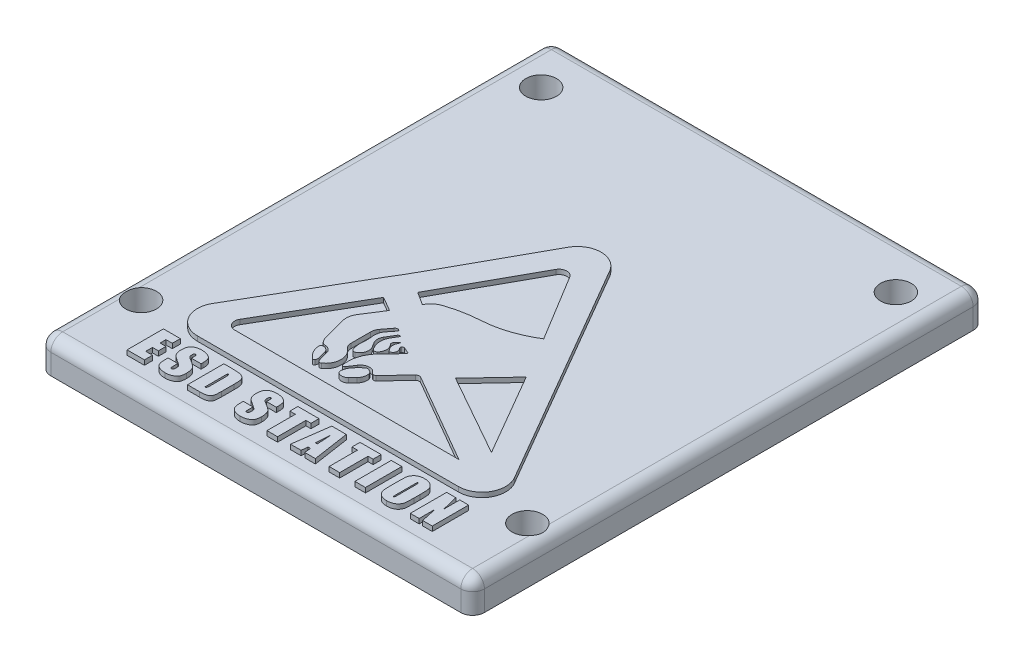
SolidWorks part; units mm, degrees
ref_plane "Front Plane" through (0, 0, 0) normal (0, 0, 1) x (1, 0, 0)
ref_plane "Top Plane" through (0, 0, 0) normal (0, 1, 0) x (1, 0, 0)
ref_plane "Right Plane" through (0, 0, 0) normal (1, 0, 0) x (0, 0, -1)
sketch "Sketch1" plane through (0, 0, 0) normal (0, 1, 0) x (1, 0, 0)
  line L1 (0, 0) -> (139.7, 0)
  line L2 (0, 0) -> (0, 165.1)
  line L3 (0, 165.1) -> (139.7, 165.1)
  line L4 (139.7, 0) -> (139.7, 165.1)
  dimension "D1" = 139.7
  dimension "D2" = 165.1
extrude "Boss-Extrude1" add sketch "Sketch1" along normal blind 9.144
fillet "Fillet1" radius 3.81 4 edges at (139.7, 4.572, -165.1) (139.7, 4.572, 0) (0, 4.572, -165.1) (0, 4.572, 0)
sketch "Sketch2" plane through (0, 9.144, 0) normal (0, 1, 0) x (1, 0, 0)
  line L0 (0, 161.29) -> (0, 3.81) construction
  line L1 (3.81, 0) -> (135.89, 0) construction
  line L2 (69.85, 0) -> (69.85, 165.1) construction
  line L3 (135.89, 165.1) -> (3.81, 165.1) construction
  line L4 (69.85, 82.55) -> (0, 82.55) construction
  circle A0 centre (12.7, 16.002) radius 3.175 construction
  circle A1 centre (127, 16.002) radius 3.175 construction
  circle A2 centre (127, 149.098) radius 3.175
  circle A3 centre (12.7, 149.098) radius 3.175
  dimension "D1" = 12.7
  dimension "D3" = 6.35
  dimension "D2" = 16.002
extrude "Cut-Extrude1" cut sketch "Sketch2" against normal up to surface (9.144 mm away) up to face at (69.85, 0, -82.55)
sketch "Sketch3" plane through (0, 9.144, 0) normal (0, 1, 0) x (1, 0, 0)
  line L0 (70.496, 137.8694) -> (270.496, 137.8694) construction
  line L1 (28.161, 30.48) -> (47.4134, 63.5939)
  line L2 (47.4134, 63.5939) -> (52.0401, 60.904)
  line L3 (52.0401, 60.904) -> (47.9409, 54.4852)
  line L4 (47.4134, 50.3026) -> (49.2236, 43.3018)
  line L5 (53.4968, 39.5889) -> (54.3392, 36.5694)
  line L6 (56.4761, 42.9358) -> (55.7165, 43.6972)
  line L7 (54.9768, 45.464) -> (54.9768, 51.8379)
  line L8 (55.7165, 54.0378) -> (57.7293, 56.6923)
  line L9 (59.2557, 55.9566) -> (57.0374, 53.1942)
  line L10 (59.4465, 47.8878) -> (58.5145, 49.4385)
  line L11 (58.5145, 52.437) -> (60.177, 55.203)
  line L12 (61.3238, 54.8213) -> (60.3568, 53.2123)
  line L13 (60.177, 48.6632) -> (60.5632, 47.8878)
  line L14 (61.3238, 52.9984) -> (62.2674, 53.9845)
  line L15 (64.9229, 53.4025) -> (66.4394, 52.6187)
  line L16 (66.7904, 51.5356) -> (62.2912, 46.8332)
  line L17 (60.5628, 38.0202) -> (62.1412, 40.4606)
  line L18 (65.7939, 41.6234) -> (66.8771, 40.5871)
  line L19 (68.0387, 40.5871) -> (74.234, 47.0623)
  line L20 (75.7475, 47.2487) -> (104.8079, 30.48)
  line L21 (104.8079, 30.48) -> (28.161, 30.48)
  line L22 (50.6207, 39.2402) -> (50.6207, 39.6797) construction
  line L23 (53.0532, 39.2402) -> (53.8778, 36.2848) construction
  line L24 (52.8363, 35.231) -> (52.0463, 36.0717) construction
  line L25 (65.5353, 36.9764) -> (64.1904, 35.5708) construction
  line L26 (51.5296, 70.4908) -> (69.493, 102.9855)
  line L27 (69.493, 102.9855) -> (84.8095, 77.8112)
  line L28 (55.7165, 67.7984) -> (51.5296, 70.4908)
  line L29 (81.5879, 52.6185) -> (92.6396, 64.3418)
  line L30 (92.6396, 64.3418) -> (108.0952, 37.6852)
  line L31 (108.0952, 37.6852) -> (81.5879, 52.6185)
  line L32 (51.1287, 39.264) -> (51.1287, 39.6797)
  line L33 (52.5794, 39.0482) -> (53.3885, 36.1483)
  line L34 (53.2776, 35.5031) -> (52.4165, 36.4195)
  line L35 (65.1682, 37.3276) -> (63.8234, 35.922)
  line L36 (3.81, 0) -> (135.89, 0) construction
  line L37 (139.7, 3.81) -> (139.7, 161.29) construction
  arc A0 (47.9409, 54.4852) -> (47.4134, 50.3026) centre (52.0861, 51.8379) ccw
  arc A1 (49.2236, 43.3018) -> (49.9905, 41.6232) centre (54.3392, 44.6245) ccw
  arc A2 (49.9905, 41.6232) -> (51.4393, 40.8175) centre (51.5296, 42.6854) ccw
  arc A3 (51.4393, 40.8175) -> (53.4968, 39.5889) centre (51.3162, 38.2743) cw
  arc A4 (54.3392, 36.5694) -> (54.7579, 35.4842) centre (60.1769, 38.1982) ccw
  arc A5 (54.7579, 35.4842) -> (55.7165, 35.231) centre (55.3488, 35.7802) ccw
  arc A6 (55.7165, 35.231) -> (56.4761, 42.9358) centre (52.928, 39.3958) ccw
  arc A7 (55.7165, 43.6972) -> (54.9768, 45.464) centre (57.5095, 45.4861) cw
  arc A8 (54.9768, 51.8379) -> (55.7165, 54.0378) centre (58.6177, 51.8379) cw
  arc A9 (57.7293, 56.6923) -> (58.6177, 57.0798) centre (58.5193, 56.0933) cw
  arc A10 (58.6177, 57.0798) -> (59.2557, 55.9566) centre (58.5392, 56.2924) cw
  arc A11 (57.0374, 53.1942) -> (56.4761, 51.1928) centre (59.1031, 51.5354) ccw
  arc A12 (56.4761, 51.1928) -> (56.5523, 47.5601) centre (39.8723, 49.0275) cw
  arc A13 (56.5523, 47.5601) -> (57.0374, 44.1483) centre (64.1142, 46.8949) ccw
  arc A14 (57.0374, 44.1483) -> (58.1466, 43.6972) centre (57.8049, 44.4461) ccw
  arc A15 (58.1466, 43.6972) -> (59.4465, 47.8878) centre (56.9259, 46.3728) ccw
  arc A16 (58.5145, 49.4385) -> (58.5145, 52.437) centre (61.0089, 50.9378) cw
  arc A17 (60.177, 55.203) -> (61.3238, 54.8213) centre (60.7077, 54.8839) cw
  arc A18 (60.3568, 53.2123) -> (60.177, 48.6632) centre (64.4138, 50.7739) ccw
  arc A19 (60.5632, 47.8878) -> (61.3238, 47.7724) centre (60.9841, 48.0975) ccw
  arc A20 (61.3238, 47.7724) -> (61.3238, 51.1928) centre (59.5364, 49.4826) ccw
  arc A21 (61.3238, 51.1928) -> (61.3238, 52.9984) centre (62.2674, 52.0956) cw
  arc A22 (62.2674, 53.9845) -> (62.8438, 53.6001) centre (62.5216, 53.7414) cw
  arc A23 (62.8438, 53.6001) -> (62.4203, 52.5384) centre (78.3715, 46.7913) ccw
  arc A24 (62.4203, 52.5384) -> (62.719, 50.2428) centre (64.8004, 51.6809) ccw
  arc A25 (62.719, 50.2428) -> (64.1904, 50.6654) centre (63.3835, 50.702) ccw
  arc A26 (64.1904, 50.6654) -> (63.828, 51.6803) centre (62.7686, 50.7298) ccw
  arc A27 (63.828, 51.6803) -> (63.828, 53.0022) centre (64.5648, 52.3412) cw
  arc A28 (63.828, 53.0022) -> (64.9229, 53.4025) centre (64.7516, 52.1737) cw
  arc A29 (66.4394, 52.6187) -> (66.7904, 51.5356) centre (66.068, 51.8999) cw
  arc A30 (62.2912, 46.8332) -> (59.6799, 38.1984) centre (69.4926, 39.9431) ccw
  arc A31 (59.6799, 38.1984) -> (60.5628, 38.0202) centre (60.1564, 38.2831) ccw
  arc A32 (62.1412, 40.4606) -> (65.7939, 41.6234) centre (64.6742, 38.8223) cw
  arc A33 (66.8771, 40.5871) -> (68.0387, 40.5871) centre (67.4579, 41.1941) ccw
  arc A34 (74.234, 47.0623) -> (75.7475, 47.2487) centre (75.1048, 46.2291) cw
  arc A35 (50.6207, 39.6797) -> (51.1953, 40.2899) centre (51.2321, 39.6797) cw construction
  arc A36 (51.1953, 40.2899) -> (53.0532, 39.2402) centre (51.3133, 38.3297) cw construction
  arc A37 (53.8778, 36.2848) -> (53.7449, 35.231) centre (52.5567, 35.9162) cw construction
  arc A38 (53.7449, 35.231) -> (52.8363, 35.231) centre (53.2906, 35.493) cw construction
  arc A39 (52.0463, 36.0717) -> (50.6207, 39.2402) centre (55.9362, 39.7268) cw construction
  arc A40 (64.1904, 35.5708) -> (61.5034, 35.231) centre (62.6376, 37.0566) cw construction
  arc A41 (61.5034, 35.231) -> (60.9841, 36.2736) centre (62.0888, 36.1732) cw construction
  arc A42 (60.9841, 36.2736) -> (62.0888, 38.9278) centre (65.7697, 35.8388) cw construction
  arc A43 (62.0888, 38.9278) -> (64.1142, 40.9166) centre (73.3944, 29.4401) cw construction
  arc A44 (64.1142, 40.9166) -> (65.4437, 40.9166) centre (64.7789, 40.0946) cw construction
  arc A45 (65.5353, 36.9764) -> (66.4399, 39.7268) centre (63.1082, 39.2986) ccw construction
  arc A46 (66.4399, 39.7268) -> (65.4437, 40.9166) centre (65.012, 39.5433) ccw construction
  arc A47 (84.8095, 77.8112) -> (80.0875, 75.3624) centre (64.5176, 111.1633) cw
  arc A48 (80.0875, 75.3624) -> (69.493, 72.8238) centre (67.6134, 104.0449) cw
  arc A49 (69.493, 72.8238) -> (59.2557, 70.8551) centre (71.9121, 32.6431) ccw
  arc A50 (59.2557, 70.8551) -> (55.7165, 67.7984) centre (61.1776, 65.0525) ccw
  arc A51 (52.4165, 36.4195) -> (51.1287, 39.264) centre (55.9362, 39.7268) cw
  arc A52 (51.1287, 39.6797) -> (51.2259, 39.7828) centre (51.2321, 39.6797) cw
  arc A53 (51.2259, 39.7828) -> (52.5794, 39.0482) centre (51.3133, 38.3297) cw
  arc A54 (53.3885, 36.1483) -> (53.3048, 35.4848) centre (52.5567, 35.9162) cw
  arc A55 (53.3048, 35.4848) -> (53.2776, 35.5031) centre (53.2906, 35.493) cw
  arc A56 (61.7715, 35.6625) -> (61.49, 36.2276) centre (62.0888, 36.1732) cw
  arc A57 (61.49, 36.2276) -> (62.4779, 38.6012) centre (65.7697, 35.8388) cw
  arc A58 (62.4779, 38.6012) -> (64.4336, 40.5216) centre (73.3944, 29.4401) cw
  arc A59 (64.4336, 40.5216) -> (65.1911, 40.4575) centre (64.7789, 40.0946) cw
  arc A60 (65.936, 39.6621) -> (65.1911, 40.4575) centre (65.012, 39.5433) ccw
  arc A61 (65.1682, 37.3276) -> (65.936, 39.6621) centre (63.1082, 39.2986) ccw
  arc A62 (63.8234, 35.922) -> (61.7715, 35.6625) centre (62.6376, 37.0566) cw
  point P134 (50.787, 40.0988)
  point P136 (53.2906, 34.9686)
  dimension "D17" = 4.9184
  dimension "D18" = 5.2839
  dimension "D19" = 1.8701
  dimension "D20" = 2.5462
  dimension "D21" = 6.0606
  dimension "D22" = 0.6609
  dimension "D23" = 2.5329
  dimension "D24" = 3.6409
  dimension "D25" = 0.9915
  dimension "D26" = 0.7913
  dimension "D27" = 2.6492
  dimension "D28" = 16.7444
  dimension "D29" = 7.5911
  dimension "D30" = 0.8232
  dimension "D31" = 2.9409
  dimension "D32" = 2.9103
  dimension "D33" = 0.6193
  dimension "D34" = 4.7335
  dimension "D35" = 0.4702
  dimension "D36" = 2.4738
  dimension "D37" = 1.3059
  dimension "D38" = 0.3518
  dimension "D39" = 16.955
  dimension "D40" = 2.5299
  dimension "D41" = 0.8078
  dimension "D42" = 1.4233
  dimension "D43" = 0.9898
  dimension "D44" = 1.2407
  dimension "D45" = 0.8091
  dimension "D46" = 9.9666
  dimension "D47" = 0.484
  dimension "D48" = 3.0166
  dimension "D49" = 0.8402
  dimension "D50" = 1.2052
  dimension "D51" = 0.6114
  dimension "D52" = 1.9637
  dimension "D53" = 1.3716
  dimension "D54" = 0.5244
  dimension "D55" = 5.3377
  dimension "D56" = 2.1492
  dimension "D57" = 1.1092
  dimension "D58" = 4.8053
  dimension "D59" = 14.7592
  dimension "D60" = 1.0572
  dimension "D61" = 3.3591
  dimension "D62" = 1.4396
  dimension "D63" = 39.04
  dimension "D64" = 31.2776
  dimension "D65" = 40.2535
  dimension "D66" = 6.1126
  dimension "D67" = 31.6048
  dimension "D68" = 34.8921
  dimension "D69" = 47.0604
  dimension "D70" = 54.8905
  dimension "D71" = 58.1121
  dimension "D72" = 59.6125
  dimension "D73" = 61.3285
  dimension "D74" = 64.5952
  dimension "D75" = 65.466
  dimension "D76" = 66.3056
  dimension "D77" = 67.7879
  dimension "D78" = 70.2074
  dimension "D3" = 4.9778
  dimension "D4" = 37.1294
  dimension "D5" = 29.4677
  dimension "D6" = 8.0318
  dimension "D7" = 7.8134
  dimension "D8" = 15.5799
  dimension "D9" = 30.8131
  dimension "D10" = 30.4243
  dimension "D11" = 7.9197
  dimension "D12" = 7.57
  dimension "D13" = 30.48
  dimension "D14" = 33.5513
  dimension "D15" = 76.6469
  dimension "D16" = 38.3039
  dimension "D79" = 71.6613
  dimension "D80" = 72.9096
  dimension "D81" = 73.2606
  dimension "D82" = 73.632
  dimension "D83" = 73.764
  dimension "D84" = 73.9061
  dimension "D85" = 73.9303
  dimension "D86" = 74.5089
  dimension "D87" = 74.5318
  dimension "D88" = 74.7771
  dimension "D89" = 74.8996
  dimension "D90" = 74.9484
  dimension "D91" = 75.0258
  dimension "D92" = 75.1352
  dimension "D93" = 75.2862
  dimension "D94" = 77.5588
  dimension "D95" = 78.5224
  dimension "D96" = 78.6911
  dimension "D97" = 78.9923
  dimension "D98" = 79.5231
  dimension "D99" = 80.5969
  dimension "D100" = 81.0823
  dimension "D101" = 81.1608
  dimension "D102" = 81.5534
  dimension "D103" = 81.9707
  dimension "D104" = 82.1905
  dimension "D105" = 83.2239
  dimension "D106" = 83.7638
  dimension "D107" = 85.3608
  dimension "D108" = 85.3608
  dimension "D109" = 86.2032
  dimension "D110" = 86.3115
  dimension "D111" = 86.772
  dimension "D112" = 87.1206
  dimension "D113" = 87.6139
  dimension "D114" = 88.2607
  dimension "D115" = 88.3867
  dimension "D1" = 0.508
  dimension "D2" = 0.508
extrude "Boss-Extrude3" add sketch "Sketch3" along normal blind 1.27
sketch "Sketch4" plane through (0, 9.144, 0) normal (0, 1, 0) x (1, 0, 0)
  line L28 (114.6873, 41.5074) -> (99.2316, 68.1639)
  line L29 (114.6873, 41.5074) -> (99.2316, 68.1639)
  line L38 (40.8259, 67.4239) -> (44.8608, 74.1774)
  line L39 (40.8259, 67.4239) -> (14.9165, 22.86)
  line L40 (14.9165, 22.86) -> (104.8079, 22.86)
  line L41 (40.8259, 67.4239) -> (21.5735, 34.31)
  line L42 (28.161, 22.86) -> (104.8079, 22.86)
  line L45 (99.2316, 68.1639) -> (76.4466, 107.4616)
  line L47 (114.6873, 41.5074) -> (118.8649, 34.3021)
  line L48 (112.2729, 22.86) -> (104.8079, 22.86)
  line L49 (44.8608, 74.1774) -> (63.1857, 107.326)
  line L50 (69.493, 102.9855) -> (51.5296, 70.4908) construction
  line L52 (139.7, 3.81) -> (139.7, 161.29) construction
  line L55 (3.81, 0) -> (135.89, 0) construction
  line L56 (135.89, 165.1) -> (3.81, 165.1) construction
  line L57 (0, 161.29) -> (0, 3.81) construction
  line L58 (139.7, 3.81) -> (139.7, 161.29)
  line L59 (3.81, 0) -> (135.89, 0)
  line L60 (135.89, 165.1) -> (3.81, 165.1)
  line L61 (0, 161.29) -> (0, 3.81)
  arc A0 (28.161, 22.86) -> (21.5735, 34.31) centre (28.161, 30.48) cw
  arc A1 (118.8649, 34.3021) -> (112.2729, 22.86) centre (112.2729, 30.48) cw
  arc A2 (76.4466, 107.4616) -> (63.1857, 107.326) centre (69.8545, 103.6394) ccw
  arc A5 (139.7, 161.29) -> (135.89, 165.1) centre (135.89, 161.29) ccw construction
  arc A6 (135.89, 0) -> (139.7, 3.81) centre (135.89, 3.81) ccw construction
  arc A7 (0, 3.81) -> (3.81, 0) centre (3.81, 3.81) ccw construction
  arc A8 (3.81, 165.1) -> (0, 161.29) centre (3.81, 161.29) ccw construction
  arc A11 (139.7, 161.29) -> (135.89, 165.1) centre (135.89, 161.29) ccw
  arc A12 (135.89, 0) -> (139.7, 3.81) centre (135.89, 3.81) ccw
  arc A13 (0, 3.81) -> (3.81, 0) centre (3.81, 3.81) ccw
  arc A14 (3.81, 165.1) -> (0, 161.29) centre (3.81, 161.29) ccw
  circle A15 centre (127, 149.098) radius 3.175 construction
  circle A16 centre (12.7, 149.098) radius 3.175 construction
  circle A17 centre (127, 149.098) radius 3.175
  circle A18 centre (12.7, 149.098) radius 3.175
  dimension "D5" = 7.62
  dimension "D3" = 7.62
  dimension "D4" = 7.867
  dimension "D1" = 7.62
  dimension "D2" = 7.62
extrude "Boss-Extrude5" add sketch "Sketch4" along normal up to surface (1.27 mm away) up to face at (59.5349, 10.414, -47.7884)
fillet "Fillet2" radius 2.54 2 edges at (69.493, 9.779, -102.9855) (28.161, 9.779, -30.48)
sketch "Sketch5" plane through (0, 10.414, 0) normal (0, 1, 0) x (1, 0, 0)
  line L2 (3.81, 7.62) -> (135.89, 7.62)
  line L3 (3.81, 7.62) -> (135.89, 7.62) construction
  text T0 "E S D  S T A T I O N" font "Impact" height in points 42
  dimension "D1" = 7.62
extrude "Boss-Extrude6" add sketch "Sketch5" along normal blind 1.524
sketch "Sketch6" plane through (0, 10.414, 0) normal (0, 1, 0) x (1, 0, 0)
  circle A0 centre (7.62, 25.273) radius 3.81 construction
  circle A1 centre (132.08, 25.273) radius 3.81 construction
  circle A2 centre (7.62, 25.273) radius 3.81 construction
  circle A3 centre (132.08, 25.273) radius 3.81 construction
  circle A4 centre (132.08, 25.273) radius 3.175
  circle A5 centre (7.62, 25.273) radius 3.175
  dimension "D1" = 6.35
  dimension "D2" = 6.35
extrude "Cut-Extrude2" cut sketch "Sketch6" against normal up to surface (10.414 mm away) up to face at (127, 0, -152.273)
sketch "Sketch7" plane through (0, 10.414, 0) normal (0, 1, 0) x (1, 0, 0)
  circle A0 centre (127, 149.098) radius 4.953
  circle A1 centre (132.08, 25.273) radius 4.953
  circle A2 centre (7.62, 25.273) radius 4.953
  circle A3 centre (12.7, 149.098) radius 4.953
  dimension "D1" = 9.906
  dimension "D2" = 9.906
  dimension "D3" = 9.906
  dimension "D4" = 9.906
extrude "Cut-Extrude3" cut sketch "Sketch7" against normal blind 6.985
fillet "Fillet3" radius 3.81 8 edges at (1.1159, 10.414, -163.9841) (69.85, 10.414, -165.1) (138.5841, 10.414, -163.9841) (139.7, 10.414, -82.55) (138.5841, 10.414, -1.1159) (69.85, 10.414, 0) (1.1159, 10.414, -1.1159) (0, 10.414, -82.55)
sketch "Sketch10" plane through (0, 9.144, 0) normal (0, 1, 0) x (1, 0, 0)
  line L0 (63.8234, 35.922) -> (65.1682, 37.3276) construction
  line L1 (51.1287, 39.6797) -> (51.1287, 39.264) construction
  line L2 (52.4165, 36.4195) -> (53.2776, 35.5031) construction
  line L3 (53.3885, 36.1483) -> (52.5794, 39.0482) construction
  line L4 (44.8608, 74.1774) -> (40.8259, 67.4239) construction
  line L5 (40.8259, 67.4239) -> (21.5735, 34.31) construction
  line L6 (28.161, 22.86) -> (112.2729, 22.86) construction
  line L7 (118.8649, 34.3021) -> (76.4466, 107.4616) construction
  line L8 (63.1857, 107.326) -> (44.8608, 74.1774) construction
  line L9 (63.8234, 35.922) -> (65.1682, 37.3276)
  line L10 (51.1287, 39.6797) -> (51.1287, 39.264)
  line L11 (52.4165, 36.4195) -> (53.2776, 35.5031)
  line L12 (53.3885, 36.1483) -> (52.5794, 39.0482)
  line L13 (44.8608, 74.1774) -> (40.8259, 67.4239)
  line L14 (40.8259, 67.4239) -> (21.5735, 34.31)
  line L15 (28.161, 22.86) -> (112.2729, 22.86)
  line L16 (118.8649, 34.3021) -> (76.4466, 107.4616)
  line L17 (63.1857, 107.326) -> (44.8608, 74.1774)
  line L18 (81.5879, 52.6185) -> (108.0952, 37.6852) construction
  line L19 (108.0952, 37.6852) -> (92.6396, 64.3418) construction
  line L20 (92.6396, 64.3418) -> (81.5879, 52.6185) construction
  line L21 (84.8095, 77.8112) -> (71.7682, 99.2461) construction
  line L22 (67.3753, 99.1547) -> (51.5296, 70.4908) construction
  line L23 (51.5296, 70.4908) -> (55.7165, 67.7984) construction
  line L24 (47.4134, 63.5939) -> (30.38, 34.2967) construction
  line L25 (32.5759, 30.48) -> (104.8079, 30.48) construction
  line L26 (104.8079, 30.48) -> (75.7475, 47.2487) construction
  line L27 (74.234, 47.0623) -> (68.0387, 40.5871) construction
  line L28 (66.8771, 40.5871) -> (65.7939, 41.6234) construction
  line L29 (62.1412, 40.4606) -> (60.5628, 38.0202) construction
  line L30 (62.2912, 46.8332) -> (66.7904, 51.5356) construction
  line L31 (66.4394, 52.6187) -> (64.9229, 53.4025) construction
  line L32 (62.2674, 53.9845) -> (61.3238, 52.9984) construction
  line L33 (60.5632, 47.8878) -> (60.177, 48.6632) construction
  line L34 (60.3568, 53.2123) -> (61.3238, 54.8213) construction
  line L35 (60.177, 55.203) -> (58.5145, 52.437) construction
  line L36 (58.5145, 49.4385) -> (59.4465, 47.8878) construction
  line L37 (57.0374, 53.1942) -> (59.2557, 55.9566) construction
  line L38 (57.7293, 56.6923) -> (55.7165, 54.0378) construction
  line L39 (54.9768, 51.8379) -> (54.9768, 45.464) construction
  line L40 (55.7165, 43.6972) -> (56.4761, 42.9358) construction
  line L41 (54.3392, 36.5694) -> (53.4968, 39.5889) construction
  line L42 (49.2236, 43.3018) -> (47.4134, 50.3026) construction
  line L43 (47.9409, 54.4852) -> (52.0401, 60.904) construction
  line L44 (52.0401, 60.904) -> (47.4134, 63.5939) construction
  line L45 (81.5879, 52.6185) -> (108.0952, 37.6852)
  line L46 (108.0952, 37.6852) -> (92.6396, 64.3418)
  line L47 (92.6396, 64.3418) -> (81.5879, 52.6185)
  line L48 (84.8095, 77.8112) -> (71.7682, 99.2461)
  line L49 (67.3753, 99.1547) -> (51.5296, 70.4908)
  line L50 (51.5296, 70.4908) -> (55.7165, 67.7984)
  line L51 (47.4134, 63.5939) -> (30.38, 34.2967)
  line L52 (32.5759, 30.48) -> (104.8079, 30.48)
  line L53 (104.8079, 30.48) -> (75.7475, 47.2487)
  line L54 (74.234, 47.0623) -> (68.0387, 40.5871)
  line L55 (66.8771, 40.5871) -> (65.7939, 41.6234)
  line L56 (62.1412, 40.4606) -> (60.5628, 38.0202)
  line L57 (62.2912, 46.8332) -> (66.7904, 51.5356)
  line L58 (66.4394, 52.6187) -> (64.9229, 53.4025)
  line L59 (62.2674, 53.9845) -> (61.3238, 52.9984)
  line L60 (60.5632, 47.8878) -> (60.177, 48.6632)
  line L61 (60.3568, 53.2123) -> (61.3238, 54.8213)
  line L62 (60.177, 55.203) -> (58.5145, 52.437)
  line L63 (58.5145, 49.4385) -> (59.4465, 47.8878)
  line L64 (57.0374, 53.1942) -> (59.2557, 55.9566)
  line L65 (57.7293, 56.6923) -> (55.7165, 54.0378)
  line L66 (54.9768, 51.8379) -> (54.9768, 45.464)
  line L67 (55.7165, 43.6972) -> (56.4761, 42.9358)
  line L68 (54.3392, 36.5694) -> (53.4968, 39.5889)
  line L69 (49.2236, 43.3018) -> (47.4134, 50.3026)
  line L70 (47.9409, 54.4852) -> (52.0401, 60.904)
  line L71 (52.0401, 60.904) -> (47.4134, 63.5939)
  arc A0 (61.49, 36.2276) -> (61.7715, 35.6625) centre (62.0888, 36.1732) ccw construction
  arc A1 (61.7715, 35.6625) -> (63.8234, 35.922) centre (62.6376, 37.0566) ccw construction
  arc A2 (65.1682, 37.3276) -> (65.936, 39.6621) centre (63.1082, 39.2986) ccw construction
  arc A3 (65.936, 39.6621) -> (65.1911, 40.4575) centre (65.012, 39.5433) ccw construction
  arc A4 (65.1911, 40.4575) -> (64.4336, 40.5216) centre (64.7789, 40.0946) ccw construction
  arc A5 (64.4336, 40.5216) -> (62.4779, 38.6012) centre (73.3944, 29.4401) ccw construction
  arc A6 (62.4779, 38.6012) -> (61.49, 36.2276) centre (65.7697, 35.8388) ccw construction
  arc A7 (51.1287, 39.264) -> (52.4165, 36.4195) centre (55.9362, 39.7268) ccw construction
  arc A8 (53.2776, 35.5031) -> (53.3048, 35.4848) centre (53.2906, 35.493) ccw construction
  arc A9 (53.3048, 35.4848) -> (53.3885, 36.1483) centre (52.5567, 35.9162) ccw construction
  arc A10 (52.5794, 39.0482) -> (51.2259, 39.7828) centre (51.3133, 38.3297) ccw construction
  arc A11 (51.2259, 39.7828) -> (51.1287, 39.6797) centre (51.2321, 39.6797) ccw construction
  arc A12 (21.5735, 34.31) -> (28.161, 22.86) centre (28.161, 30.48) ccw construction
  arc A13 (112.2729, 22.86) -> (118.8649, 34.3021) centre (112.2729, 30.48) ccw construction
  arc A14 (76.4466, 107.4616) -> (63.1857, 107.326) centre (69.8545, 103.6394) ccw construction
  arc A15 (61.49, 36.2276) -> (61.7715, 35.6625) centre (62.0888, 36.1732) ccw
  arc A16 (61.7715, 35.6625) -> (63.8234, 35.922) centre (62.6376, 37.0566) ccw
  arc A17 (65.1682, 37.3276) -> (65.936, 39.6621) centre (63.1082, 39.2986) ccw
  arc A18 (65.936, 39.6621) -> (65.1911, 40.4575) centre (65.012, 39.5433) ccw
  arc A19 (65.1911, 40.4575) -> (64.4336, 40.5216) centre (64.7789, 40.0946) ccw
  arc A20 (64.4336, 40.5216) -> (62.4779, 38.6012) centre (73.3944, 29.4401) ccw
  arc A21 (62.4779, 38.6012) -> (61.49, 36.2276) centre (65.7697, 35.8388) ccw
  arc A22 (51.1287, 39.264) -> (52.4165, 36.4195) centre (55.9362, 39.7268) ccw
  arc A23 (53.2776, 35.5031) -> (53.3048, 35.4848) centre (53.2906, 35.493) ccw
  arc A24 (53.3048, 35.4848) -> (53.3885, 36.1483) centre (52.5567, 35.9162) ccw
  arc A25 (52.5794, 39.0482) -> (51.2259, 39.7828) centre (51.3133, 38.3297) ccw
  arc A26 (51.2259, 39.7828) -> (51.1287, 39.6797) centre (51.2321, 39.6797) ccw
  arc A27 (21.5735, 34.31) -> (28.161, 22.86) centre (28.161, 30.48) ccw
  arc A28 (112.2729, 22.86) -> (118.8649, 34.3021) centre (112.2729, 30.48) ccw
  arc A29 (76.4466, 107.4616) -> (63.1857, 107.326) centre (69.8545, 103.6394) ccw
  arc A30 (71.7682, 99.2461) -> (67.3753, 99.1547) centre (69.5983, 97.9258) ccw construction
  arc A31 (59.2557, 70.8551) -> (55.7165, 67.7984) centre (61.1776, 65.0525) ccw construction
  arc A32 (69.493, 72.8238) -> (59.2557, 70.8551) centre (71.9121, 32.6431) ccw construction
  arc A33 (69.493, 72.8238) -> (80.0875, 75.3624) centre (67.6134, 104.0449) ccw construction
  arc A34 (80.0875, 75.3624) -> (84.8095, 77.8112) centre (64.5176, 111.1633) ccw construction
  arc A35 (30.38, 34.2967) -> (32.5759, 30.48) centre (32.5759, 33.02) ccw construction
  arc A36 (75.7475, 47.2487) -> (74.234, 47.0623) centre (75.1048, 46.2291) ccw construction
  arc A37 (66.8771, 40.5871) -> (68.0387, 40.5871) centre (67.4579, 41.1941) ccw construction
  arc A38 (65.7939, 41.6234) -> (62.1412, 40.4606) centre (64.6742, 38.8223) ccw construction
  arc A39 (59.6799, 38.1984) -> (60.5628, 38.0202) centre (60.1564, 38.2831) ccw construction
  arc A40 (62.2912, 46.8332) -> (59.6799, 38.1984) centre (69.4926, 39.9431) ccw construction
  arc A41 (66.7904, 51.5356) -> (66.4394, 52.6187) centre (66.068, 51.8999) ccw construction
  arc A42 (64.9229, 53.4025) -> (63.828, 53.0022) centre (64.7516, 52.1737) ccw construction
  arc A43 (63.828, 53.0022) -> (63.828, 51.6803) centre (64.5648, 52.3412) ccw construction
  arc A44 (64.1904, 50.6654) -> (63.828, 51.6803) centre (62.7686, 50.7298) ccw construction
  arc A45 (62.719, 50.2428) -> (64.1904, 50.6654) centre (63.3835, 50.702) ccw construction
  arc A46 (62.4203, 52.5384) -> (62.719, 50.2428) centre (64.8004, 51.6809) ccw construction
  arc A47 (62.8438, 53.6001) -> (62.4203, 52.5384) centre (78.3715, 46.7913) ccw construction
  arc A48 (62.8438, 53.6001) -> (62.2674, 53.9845) centre (62.5216, 53.7414) ccw construction
  arc A49 (61.3238, 52.9984) -> (61.3238, 51.1928) centre (62.2674, 52.0956) ccw construction
  arc A50 (61.3238, 47.7724) -> (61.3238, 51.1928) centre (59.5364, 49.4826) ccw construction
  arc A51 (60.5632, 47.8878) -> (61.3238, 47.7724) centre (60.9841, 48.0975) ccw construction
  arc A52 (60.3568, 53.2123) -> (60.177, 48.6632) centre (64.4138, 50.7739) ccw construction
  arc A53 (61.3238, 54.8213) -> (60.177, 55.203) centre (60.7077, 54.8839) ccw construction
  arc A54 (58.5145, 52.437) -> (58.5145, 49.4385) centre (61.0089, 50.9378) ccw construction
  arc A55 (58.1466, 43.6972) -> (59.4465, 47.8878) centre (56.9259, 46.3728) ccw construction
  arc A56 (57.0374, 44.1483) -> (58.1466, 43.6972) centre (57.8049, 44.4461) ccw construction
  arc A57 (56.5523, 47.5601) -> (57.0374, 44.1483) centre (64.1142, 46.8949) ccw construction
  arc A58 (56.5523, 47.5601) -> (56.4761, 51.1928) centre (39.8723, 49.0275) ccw construction
  arc A59 (57.0374, 53.1942) -> (56.4761, 51.1928) centre (59.1031, 51.5354) ccw construction
  arc A60 (59.2557, 55.9566) -> (58.6177, 57.0798) centre (58.5392, 56.2924) ccw construction
  arc A61 (58.6177, 57.0798) -> (57.7293, 56.6923) centre (58.5193, 56.0933) ccw construction
  arc A62 (55.7165, 54.0378) -> (54.9768, 51.8379) centre (58.6177, 51.8379) ccw construction
  arc A63 (54.9768, 45.464) -> (55.7165, 43.6972) centre (57.5095, 45.4861) ccw construction
  arc A64 (55.7165, 35.231) -> (56.4761, 42.9358) centre (52.928, 39.3958) ccw construction
  arc A65 (54.7579, 35.4842) -> (55.7165, 35.231) centre (55.3488, 35.7802) ccw construction
  arc A66 (54.3392, 36.5694) -> (54.7579, 35.4842) centre (60.1769, 38.1982) ccw construction
  arc A67 (53.4968, 39.5889) -> (51.4393, 40.8175) centre (51.3162, 38.2743) ccw construction
  arc A68 (49.9905, 41.6232) -> (51.4393, 40.8175) centre (51.5296, 42.6854) ccw construction
  arc A69 (49.2236, 43.3018) -> (49.9905, 41.6232) centre (54.3392, 44.6245) ccw construction
  arc A70 (47.9409, 54.4852) -> (47.4134, 50.3026) centre (52.0861, 51.8379) ccw construction
  arc A71 (71.7682, 99.2461) -> (67.3753, 99.1547) centre (69.5983, 97.9258) ccw
  arc A72 (59.2557, 70.8551) -> (55.7165, 67.7984) centre (61.1776, 65.0525) ccw
  arc A73 (69.493, 72.8238) -> (59.2557, 70.8551) centre (71.9121, 32.6431) ccw
  arc A74 (69.493, 72.8238) -> (80.0875, 75.3624) centre (67.6134, 104.0449) ccw
  arc A75 (80.0875, 75.3624) -> (84.8095, 77.8112) centre (64.5176, 111.1633) ccw
  arc A76 (30.38, 34.2967) -> (32.5759, 30.48) centre (32.5759, 33.02) ccw
  arc A77 (75.7475, 47.2487) -> (74.234, 47.0623) centre (75.1048, 46.2291) ccw
  arc A78 (66.8771, 40.5871) -> (68.0387, 40.5871) centre (67.4579, 41.1941) ccw
  arc A79 (65.7939, 41.6234) -> (62.1412, 40.4606) centre (64.6742, 38.8223) ccw
  arc A80 (59.6799, 38.1984) -> (60.5628, 38.0202) centre (60.1564, 38.2831) ccw
  arc A81 (62.2912, 46.8332) -> (59.6799, 38.1984) centre (69.4926, 39.9431) ccw
  arc A82 (66.7904, 51.5356) -> (66.4394, 52.6187) centre (66.068, 51.8999) ccw
  arc A83 (64.9229, 53.4025) -> (63.828, 53.0022) centre (64.7516, 52.1737) ccw
  arc A84 (63.828, 53.0022) -> (63.828, 51.6803) centre (64.5648, 52.3412) ccw
  arc A85 (64.1904, 50.6654) -> (63.828, 51.6803) centre (62.7686, 50.7298) ccw
  arc A86 (62.719, 50.2428) -> (64.1904, 50.6654) centre (63.3835, 50.702) ccw
  arc A87 (62.4203, 52.5384) -> (62.719, 50.2428) centre (64.8004, 51.6809) ccw
  arc A88 (62.8438, 53.6001) -> (62.4203, 52.5384) centre (78.3715, 46.7913) ccw
  arc A89 (62.8438, 53.6001) -> (62.2674, 53.9845) centre (62.5216, 53.7414) ccw
  arc A90 (61.3238, 52.9984) -> (61.3238, 51.1928) centre (62.2674, 52.0956) ccw
  arc A91 (61.3238, 47.7724) -> (61.3238, 51.1928) centre (59.5364, 49.4826) ccw
  arc A92 (60.5632, 47.8878) -> (61.3238, 47.7724) centre (60.9841, 48.0975) ccw
  arc A93 (60.3568, 53.2123) -> (60.177, 48.6632) centre (64.4138, 50.7739) ccw
  arc A94 (61.3238, 54.8213) -> (60.177, 55.203) centre (60.7077, 54.8839) ccw
  arc A95 (58.5145, 52.437) -> (58.5145, 49.4385) centre (61.0089, 50.9378) ccw
  arc A96 (58.1466, 43.6972) -> (59.4465, 47.8878) centre (56.9259, 46.3728) ccw
  arc A97 (57.0374, 44.1483) -> (58.1466, 43.6972) centre (57.8049, 44.4461) ccw
  arc A98 (56.5523, 47.5601) -> (57.0374, 44.1483) centre (64.1142, 46.8949) ccw
  arc A99 (56.5523, 47.5601) -> (56.4761, 51.1928) centre (39.8723, 49.0275) ccw
  arc A100 (57.0374, 53.1942) -> (56.4761, 51.1928) centre (59.1031, 51.5354) ccw
  arc A101 (59.2557, 55.9566) -> (58.6177, 57.0798) centre (58.5392, 56.2924) ccw
  arc A102 (58.6177, 57.0798) -> (57.7293, 56.6923) centre (58.5193, 56.0933) ccw
  arc A103 (55.7165, 54.0378) -> (54.9768, 51.8379) centre (58.6177, 51.8379) ccw
  arc A104 (54.9768, 45.464) -> (55.7165, 43.6972) centre (57.5095, 45.4861) ccw
  arc A105 (55.7165, 35.231) -> (56.4761, 42.9358) centre (52.928, 39.3958) ccw
  arc A106 (54.7579, 35.4842) -> (55.7165, 35.231) centre (55.3488, 35.7802) ccw
  arc A107 (54.3392, 36.5694) -> (54.7579, 35.4842) centre (60.1769, 38.1982) ccw
  arc A108 (53.4968, 39.5889) -> (51.4393, 40.8175) centre (51.3162, 38.2743) ccw
  arc A109 (49.9905, 41.6232) -> (51.4393, 40.8175) centre (51.5296, 42.6854) ccw
  arc A110 (49.2236, 43.3018) -> (49.9905, 41.6232) centre (54.3392, 44.6245) ccw
  arc A111 (47.9409, 54.4852) -> (47.4134, 50.3026) centre (52.0861, 51.8379) ccw
extrude "Boss-Extrude9" add sketch "Sketch10" along normal up to surface (2.794 mm away) contours L16 A29 L17 L13 L14 A27 L15 A28 L47 L46 L45 A75 A74 A73 A72 L50 L49 A71 L48 L70 A111 L69 A110 A109 A108 L68 A107 A106 A105 L67 A104 L66 A103 L65 A102 A101 L64 A100 A99 A98 A97 A96 L63 A95 L62 A94 L61 A93 | A20 A21 A15 A16 L9 A17 A18 A19 | A25 A26 L10 A22 L11 A23 A24 L12 region at (63.7779, 9.144, -37.9415) region at (52.2432, 9.144, -37.8945) region at (71.4284, 9.144, -55.091) up to face at (24.6097, 11.938, -13.5219)
sketch "Sketch12" plane through (0, 11.938, 0) normal (0, 1, 0) x (1, 0, 0)
  line L8 (64.1904, 35.5708) -> (65.5353, 36.9764)
  line L9 (50.6207, 39.6797) -> (50.6207, 39.2402)
  line L10 (52.0463, 36.0717) -> (52.8363, 35.231)
  line L11 (53.8778, 36.2848) -> (53.0532, 39.2402)
  line L12 (50.6207, 39.6797) -> (50.6207, 39.2402)
  line L13 (52.0463, 36.0717) -> (52.8363, 35.231)
  line L14 (53.8778, 36.2848) -> (53.0532, 39.2402)
  line L15 (64.1904, 35.5708) -> (65.5353, 36.9764)
  line L33 (64.8527, 52.8994) -> (66.8682, 52.0195)
  line L34 (60.8884, 55.083) -> (61.0705, 55.3859)
  line L35 (62.719, 50.2428) -> (63.3835, 49.3862)
  line L36 (61.6909, 52.6472) -> (62.6345, 53.6334)
  line L37 (59.7223, 48.4367) -> (60.1085, 47.6613)
  line L38 (60.8884, 55.083) -> (59.9213, 53.474)
  line L39 (61.6909, 52.6472) -> (62.6345, 53.6334)
  line L40 (59.7223, 48.4367) -> (60.1085, 47.6613)
  line L41 (60.8884, 55.083) -> (59.9213, 53.474)
  line L42 (61.0705, 55.3859) -> (66.8682, 53.6001)
  line L43 (66.8682, 53.6001) -> (66.8682, 52.0195)
  arc A15 (51.1953, 40.2899) -> (50.6207, 39.6797) centre (51.2321, 39.6797) ccw
  arc A16 (50.6207, 39.2402) -> (52.0463, 36.0717) centre (55.9362, 39.7268) ccw
  arc A17 (52.8363, 35.231) -> (53.7449, 35.231) centre (53.2906, 35.493) ccw
  arc A18 (53.7449, 35.231) -> (53.8778, 36.2848) centre (52.5567, 35.9162) ccw
  arc A19 (53.0532, 39.2402) -> (51.1953, 40.2899) centre (51.3133, 38.3297) ccw
  arc A20 (51.1953, 40.2899) -> (50.6207, 39.6797) centre (51.2321, 39.6797) ccw
  arc A21 (50.6207, 39.2402) -> (52.0463, 36.0717) centre (55.9362, 39.7268) ccw
  arc A22 (52.8363, 35.231) -> (53.7449, 35.231) centre (53.2906, 35.493) ccw
  arc A23 (53.7449, 35.231) -> (53.8778, 36.2848) centre (52.5567, 35.9162) ccw
  arc A24 (53.0532, 39.2402) -> (51.1953, 40.2899) centre (51.3133, 38.3297) ccw
  arc A34 (62.0888, 38.9278) -> (60.9841, 36.2736) centre (65.7697, 35.8388) ccw
  arc A35 (60.9841, 36.2736) -> (61.5034, 35.231) centre (62.0888, 36.1732) ccw
  arc A36 (61.5034, 35.231) -> (64.1904, 35.5708) centre (62.6376, 37.0566) ccw
  arc A37 (65.5353, 36.9764) -> (66.4399, 39.7268) centre (63.1082, 39.2986) ccw
  arc A38 (66.4399, 39.7268) -> (65.4437, 40.9166) centre (65.012, 39.5433) ccw
  arc A39 (65.4437, 40.9166) -> (64.1142, 40.9166) centre (64.7789, 40.0946) ccw
  arc A40 (64.1142, 40.9166) -> (62.0888, 38.9278) centre (73.3944, 29.4401) ccw
  arc A41 (62.0888, 38.9278) -> (60.9841, 36.2736) centre (65.7697, 35.8388) ccw
  arc A42 (60.9841, 36.2736) -> (61.5034, 35.231) centre (62.0888, 36.1732) ccw
  arc A43 (61.5034, 35.231) -> (64.1904, 35.5708) centre (62.6376, 37.0566) ccw
  arc A44 (65.5353, 36.9764) -> (66.4399, 39.7268) centre (63.1082, 39.2986) ccw
  arc A45 (66.4399, 39.7268) -> (65.4437, 40.9166) centre (65.012, 39.5433) ccw
  arc A46 (65.4437, 40.9166) -> (64.1142, 40.9166) centre (64.7789, 40.0946) ccw
  arc A47 (64.1142, 40.9166) -> (62.0888, 38.9278) centre (73.3944, 29.4401) ccw
  arc A70 (61.6909, 52.6472) -> (61.6909, 51.544) centre (62.2674, 52.0956) ccw
  arc A71 (61.6909, 47.4213) -> (61.6909, 51.544) centre (59.5364, 49.4826) ccw
  arc A72 (60.1085, 47.6613) -> (61.6909, 47.4213) centre (60.9841, 48.0975) ccw
  arc A73 (59.9213, 53.474) -> (59.7223, 48.4367) centre (64.4138, 50.7739) ccw
  arc A74 (61.6909, 52.6472) -> (61.6909, 51.544) centre (62.2674, 52.0956) ccw
  arc A75 (61.6909, 47.4213) -> (61.6909, 51.544) centre (59.5364, 49.4826) ccw
  arc A76 (60.1085, 47.6613) -> (61.6909, 47.4213) centre (60.9841, 48.0975) ccw
  arc A77 (59.9213, 53.474) -> (59.7223, 48.4367) centre (64.4138, 50.7739) ccw
  arc A84 (66.7904, 51.5356) -> (66.4394, 52.6187) centre (66.068, 51.8999) ccw construction
  arc A85 (61.3238, 54.8213) -> (60.177, 55.203) centre (60.7077, 54.8839) ccw construction
  arc A86 (62.4203, 52.5384) -> (62.719, 50.2428) centre (64.8004, 51.6809) ccw construction
  arc A87 (62.8438, 53.6001) -> (62.4203, 52.5384) centre (78.3715, 46.7913) ccw construction
  arc A88 (62.301, 49.9541) -> (64.6979, 50.6425) centre (63.3835, 50.702) ccw
  arc A89 (64.6979, 50.6425) -> (64.2062, 52.0195) centre (62.7686, 50.7298) ccw
  arc A90 (64.8527, 52.8994) -> (64.2062, 52.663) centre (64.7516, 52.1737) ccw
  arc A91 (64.2062, 52.663) -> (64.2062, 52.0195) centre (64.5648, 52.3412) ccw
  arc A92 (62.6345, 53.6334) -> (62.8438, 53.6001) centre (62.7276, 53.5443) cw
  arc A93 (64.6979, 50.6425) -> (64.2062, 52.0195) centre (62.7686, 50.7298) ccw
  arc A94 (64.8527, 52.8994) -> (64.2062, 52.663) centre (64.7516, 52.1737) ccw
  arc A95 (64.2062, 52.663) -> (64.2062, 52.0195) centre (64.5648, 52.3412) ccw
  arc A96 (62.4203, 52.5384) -> (62.719, 50.2428) centre (64.8004, 51.6809) ccw
  arc A97 (62.8438, 53.6001) -> (62.4203, 52.5384) centre (78.3715, 46.7913) ccw
  arc A98 (63.3835, 49.3862) -> (64.6979, 50.6425) centre (63.3835, 50.702) ccw
  dimension "D1" = 0.508
  dimension "D2" = 0.508
  dimension "D3" = 0.508
  dimension "D4" = 0.508
extrude "Boss-Extrude11" add sketch "Sketch12" against normal up to surface (1.524 mm away) up to face at (59.0815, 10.414, -47.5406)
sketch "Sketch13" plane through (0, 11.938, 0) normal (0, 1, 0) x (1, 0, 0)
  line L0 (56.5523, 52.2508) -> (56.6241, 52.6837)
  line L1 (57.2479, 54.1005) -> (58.9942, 56.3274)
  line L2 (59.2557, 55.9566) -> (57.0374, 53.1942) construction
  line L3 (59.2557, 55.9566) -> (57.0374, 53.1942)
  arc A0 (57.0374, 53.1942) -> (56.4761, 51.1928) centre (59.1031, 51.5354) ccw construction
  arc A1 (56.6241, 52.6837) -> (57.2479, 54.1005) centre (59.7067, 52.1723) cw
  arc A2 (58.9942, 56.3274) -> (59.0964, 56.8542) centre (58.5311, 56.6906) ccw
  arc A3 (59.2557, 55.9566) -> (58.6177, 57.0798) centre (58.5392, 56.2924) ccw construction
  arc A4 (57.0374, 53.1942) -> (56.4761, 51.1928) centre (59.1031, 51.5354) ccw construction
  arc A5 (57.0374, 53.1942) -> (56.5523, 52.2508) centre (59.1031, 51.5354) ccw
  arc A6 (59.2557, 55.9566) -> (59.0964, 56.8542) centre (58.5392, 56.2924) ccw
extrude "Boss-Extrude12" add sketch "Sketch13" against normal up to surface (1.524 mm away) up to face at (59.2412, 10.414, -47.5831)
